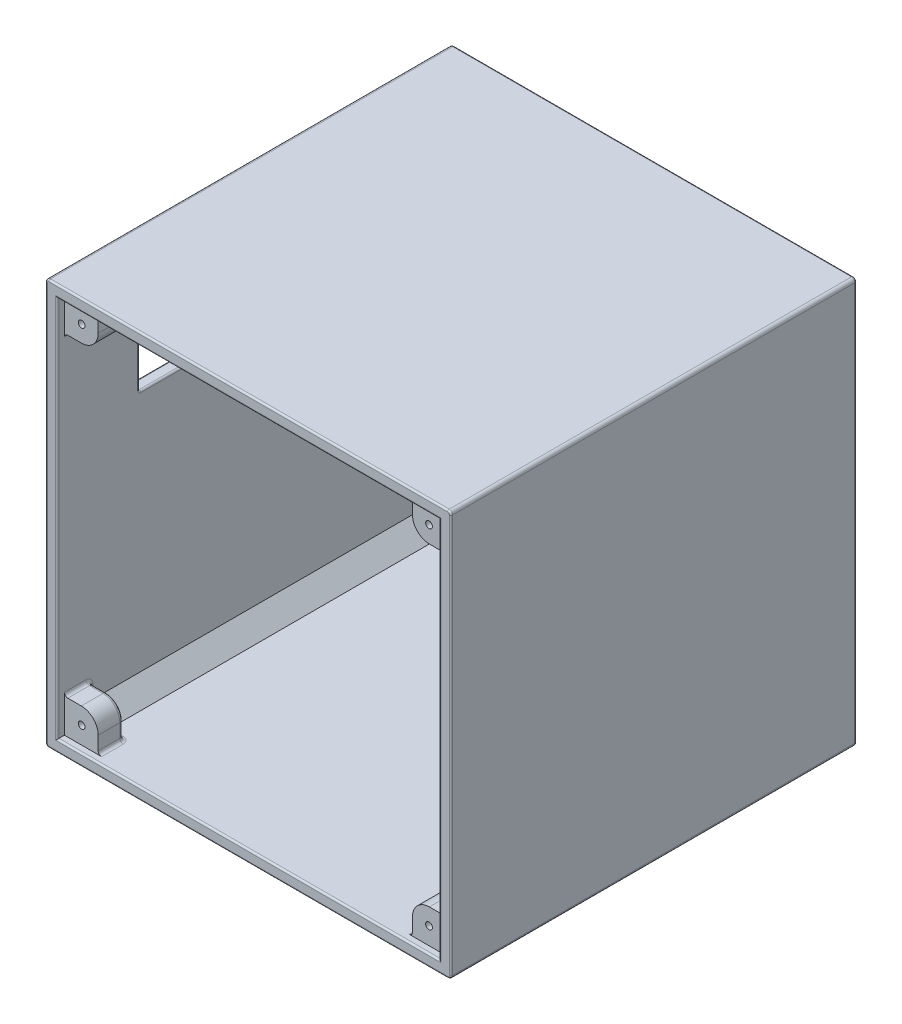
SolidWorks part; units mm, degrees
material "PVC 0.007 Plasticizado"
ref_plane "Plano frontal" through (0, 0, 0) normal (0, 0, 1) x (1, 0, 0)
ref_plane "Plano superior" through (0, 0, 0) normal (0, 1, 0) x (1, 0, 0)
ref_plane "Plano direito" through (0, 0, 0) normal (1, 0, 0) x (0, 0, -1)
sketch "Esboço2" plane through (0, 0, 0) normal (0, 0, 1) x (1, 0, 0)
  line L1 (-60, -60) -> (60, -60)
  line L2 (-60, -60) -> (-60, 60)
  line L3 (-60, 60) -> (60, 60)
  line L4 (60, -60) -> (60, 60)
  line L5 (-60, -60) -> (60, 60) construction
  line L6 (-60, 60) -> (60, -60) construction
  point P0 (0, 0)
extrude "Ressalto-extrusão1" add sketch "Esboço2" along normal blind 120
sketch "Esboço3" plane through (0, 0, 120) normal (0, 0, 1) x (1, 0, 0)
  line L8 (56.5, -56.5) -> (56.5, 56.5)
  line L9 (56.5, 56.5) -> (-56.5, 56.5)
  line L10 (-56.5, 56.5) -> (-56.5, -56.5)
  line L11 (-56.5, -56.5) -> (56.5, -56.5)
  line L12 (56.5, -56.5) -> (56.5, 56.5)
  line L13 (56.5, 56.5) -> (-56.5, 56.5)
  line L14 (-56.5, 56.5) -> (-56.5, -56.5)
  line L15 (-56.5, -56.5) -> (56.5, -56.5)
  dimension "D1" = 3.5
extrude "Corte-extrusão1" cut sketch "Esboço3" against normal blind 120
ref_plane "Plano1" through (0, 0, 0) normal (0, 0, 1) x (1, 0, 0)
ref_plane "Plano2" through (0, 0, 116.5) normal (0, 0, 1) x (1, 0, 0)
sketch "Esboço4" plane through (0, 0, 0) normal (0, 0, 1) x (1, 0, 0)
  line L0 (56.5, 56.5) -> (-56.5, 56.5) construction
  line L1 (-56.5, 56.5) -> (-56.5, -56.5) construction
  line L2 (-51.5, 46.5) -> (-56.5, 46.5)
  line L3 (-56.5, 46.5) -> (-56.5, 56.5)
  line L4 (-56.5, 56.5) -> (-46.5, 56.5)
  line L5 (-46.5, 56.5) -> (-46.5, 51.5)
  line L6 (0, -66) -> (0, 66) construction
  line L7 (46.5, 56.5) -> (46.5, 51.5)
  line L8 (56.5, 56.5) -> (46.5, 56.5)
  line L9 (56.5, 46.5) -> (56.5, 56.5)
  line L10 (51.5, 46.5) -> (56.5, 46.5)
  line L11 (66, 0) -> (-66, 0) construction
  line L12 (51.5, -46.5) -> (56.5, -46.5)
  line L13 (56.5, -46.5) -> (56.5, -56.5)
  line L14 (56.5, -56.5) -> (46.5, -56.5)
  line L15 (46.5, -56.5) -> (46.5, -51.5)
  line L16 (-46.5, -56.5) -> (-46.5, -51.5)
  line L17 (-56.5, -56.5) -> (-46.5, -56.5)
  line L18 (-56.5, -46.5) -> (-56.5, -56.5)
  line L19 (-51.5, -46.5) -> (-56.5, -46.5)
  line L20 (-51.5, 5) -> (-56.5, 5)
  line L21 (-56.5, 5) -> (-56.5, -5)
  line L22 (-56.5, -5) -> (-51.5, -5)
  line L23 (56.5, -5) -> (51.5, -5)
  line L24 (56.5, 5) -> (56.5, -5)
  line L25 (51.5, 5) -> (56.5, 5)
  line L26 (-5, 51.5) -> (-5, 56.5)
  line L27 (-5, 56.5) -> (5, 56.5)
  line L28 (5, 56.5) -> (5, 51.5)
  arc A0 (-51.5, 46.5) -> (-46.5, 51.5) centre (-51.5, 51.5) ccw
  arc A1 (51.5, 46.5) -> (46.5, 51.5) centre (51.5, 51.5) cw
  arc A2 (51.5, -46.5) -> (46.5, -51.5) centre (51.5, -51.5) ccw
  arc A3 (-51.5, -46.5) -> (-46.5, -51.5) centre (-51.5, -51.5) cw
  arc A4 (-51.5, -5) -> (-51.5, 5) centre (-51.5, 0) ccw
  arc A5 (51.5, -5) -> (51.5, 5) centre (51.5, 0) cw
  arc A6 (-5, 51.5) -> (5, 51.5) centre (0, 51.5) ccw
  dimension "D1" = 10
  dimension "D2" = 10
  dimension "D3" = 10
extrude "Ressalto-extrusão2" add sketch "Esboço4" along normal blind 7
sketch "Esboço5" plane through (0, 0, 116.5) normal (0, 0, 1) x (1, 0, 0)
  line L0 (-51.5, 46.5) -> (-56.5, 46.5)
  line L1 (-56.5, 46.5) -> (-56.5, 56.5)
  line L2 (-56.5, 56.5) -> (-46.5, 56.5)
  line L3 (-46.5, 56.5) -> (-46.5, 51.5)
  line L4 (46.5, 56.5) -> (46.5, 51.5)
  line L5 (56.5, 56.5) -> (46.5, 56.5)
  line L6 (56.5, 46.5) -> (56.5, 56.5)
  line L7 (51.5, 46.5) -> (56.5, 46.5)
  line L8 (51.5, -46.5) -> (56.5, -46.5)
  line L9 (56.5, -46.5) -> (56.5, -56.5)
  line L10 (56.5, -56.5) -> (46.5, -56.5)
  line L11 (46.5, -56.5) -> (46.5, -51.5)
  line L12 (-46.5, -56.5) -> (-46.5, -51.5)
  line L13 (-56.5, -56.5) -> (-46.5, -56.5)
  line L14 (-56.5, -46.5) -> (-56.5, -56.5)
  line L15 (-51.5, -46.5) -> (-56.5, -46.5)
  arc A0 (-51.5, 46.5) -> (-46.5, 51.5) centre (-51.5, 51.5) ccw
  arc A1 (51.5, 46.5) -> (46.5, 51.5) centre (51.5, 51.5) cw
  arc A2 (51.5, -46.5) -> (46.5, -51.5) centre (51.5, -51.5) ccw
  arc A3 (-51.5, -46.5) -> (-46.5, -51.5) centre (-51.5, -51.5) cw
  dimension "D1" = 10
ref_plane "Plano5" through (0, 0, 117.9) normal (0, 0, 1) x (1, 0, 0)
sketch "Esboço13" plane through (0, 0, 0) normal (0, 0, 1) x (1, 0, 0)
  line L0 (-56.5, -56.5) -> (56.5, -56.5) construction
  line L1 (-5, -51.5) -> (-5, -56.5)
  line L2 (-5, -56.5) -> (5, -56.5)
  line L3 (5, -56.5) -> (5, -51.5)
  arc A0 (5, -51.5) -> (-5, -51.5) centre (0, -51.5) ccw
  dimension "D1" = 10
extrude "Ressalto-extrusão6" add sketch "Esboço13" along normal blind 7
chamfer "Chanfro1" distance 5 angle 45 1 edges at (-56.5, 56.5, 63.5)
chamfer "Chanfro2" distance 5 angle 45 3 edges at (-56.5, -56.5, 63.5) (56.5, -56.5, 63.5) (56.5, 56.5, 63.5)
sketch "Esboço14" plane through (-60, 0, 0) normal (-1, 0, 0) x (0, 0, 1)
  line L0 (120, 60) -> (0, 60) construction
  line L1 (24.25, 45) -> (95.75, 45)
  line L2 (24.25, 45) -> (24.25, 20.5)
  line L3 (24.25, 20.5) -> (95.75, 20.5)
  line L4 (95.75, 45) -> (95.75, 20.5)
  line L5 (24.25, 45) -> (95.75, 20.5) construction
  line L6 (24.25, 20.5) -> (95.75, 45) construction
  point P0 (60, 32.75)
  point P8 (60, 60)
  dimension "D1" = 71.5
  dimension "D2" = 24.5
  dimension "D3" = 15
extrude "Corte-extrusão6" cut sketch "Esboço14" against normal blind 10
sketch "Esboço15" plane through (0, 0, 120) normal (0, 0, 1) x (1, 0, 0)
  line L1 (-56.5, -56.5) -> (56.5, -56.5)
  line L2 (-56.5, -56.5) -> (-56.5, 56.5)
  line L3 (-56.5, 56.5) -> (56.5, 56.5)
  line L4 (56.5, -56.5) -> (56.5, 56.5)
  line L5 (-56.5, -56.5) -> (56.5, 56.5) construction
  line L6 (-56.5, 56.5) -> (56.5, -56.5) construction
  point P0 (0, 0)
  dimension "D1" = 113
extrude "Corte-extrusão7" cut sketch "Esboço15" against normal blind 5
fillet "Filete3" radius 1 1 edges at (-60, 60, 60)
fillet "Filete4" radius 1 3 edges at (60, 60, 60) (60, -60, 60) (-60, -60, 60)
extrude "Ressalto-extrusão7" add sketch "Esboço5" against normal blind 6 and the other way blind 1.4
fillet "Filete8" radius 1 88 edges at (56.5, 46.5, 3.5) (46.5, 56.5, 3.5) (54, 46.5, 7) (47.9645, 47.9645, 7) (46.5, 54, 7) (49, 56.5, 7) (54, 54, 7) (56.5, 49, 7) (56.5, -46.5, 114.2) (46.5, -56.5, 114.2) (-46.5, -56.5, 114.2) (-56.5, -46.5, 114.2) (-56.5, 46.5, 114.2) (-46.5, 56.5, 114.2) (46.5, 56.5, 114.2) (56.5, 46.5, 114.2) (56.5, 5, 3.5) (56.5, -5, 3.5) (46.5, -56.5, 3.5) (56.5, -46.5, 3.5) (5, -56.5, 3.5) (-5, -56.5, 3.5) (-56.5, -46.5, 3.5) (-46.5, -56.5, 3.5) (-56.5, -5, 3.5) (-56.5, 5, 3.5) (-46.5, 56.5, 3.5) (-56.5, 46.5, 3.5) (-5, 56.5, 3.5) (5, 56.5, 3.5) (54, -46.5, 110.5) (47.9645, -47.9645, 110.5) (46.5, -54, 110.5) (49, -56.5, 110.5) (54, -54, 110.5) (56.5, -49, 110.5) (-49, -56.5, 110.5) (-46.5, -54, 110.5) (-47.9645, -47.9645, 110.5) (-54, -46.5, 110.5) (-56.5, -49, 110.5) (-54, -54, 110.5) (-54, 46.5, 110.5) (-47.9645, 47.9645, 110.5) (-46.5, 54, 110.5) (-49, 56.5, 110.5) (-54, 54, 110.5) (-56.5, 49, 110.5) (49, 56.5, 110.5) (46.5, 54, 110.5) (47.9645, 47.9645, 110.5) (54, 46.5, 110.5) (56.5, 49, 110.5) (54, 54, 110.5) (54, 5, 7) (56.5, 0, 7) (54, -5, 7) (46.5, 0, 7) (46.5, -54, 7) (47.9645, -47.9645, 7) (54, -46.5, 7) (56.5, -49, 7) (54, -54, 7) (49, -56.5, 7) (5, -54, 7) (0, -56.5, 7) (-5, -54, 7) (0, -46.5, 7) (-54, -46.5, 7) (-47.9645, -47.9645, 7) (-46.5, -54, 7) (-49, -56.5, 7) (-54, -54, 7) (-56.5, -49, 7) (-54, -5, 7) (-56.5, 0, 7) (-54, 5, 7) (-46.5, 0, 7) (-46.5, 54, 7) (-47.9645, 47.9645, 7) (-54, 46.5, 7) (-56.5, 49, 7) (-54, 54, 7) (-49, 56.5, 7) (0, 46.5, 7) (-5, 54, 7) (0, 56.5, 7) (5, 54, 7)
sketch "Esboço16" plane through (0, 0, 117.9) normal (0, 0, 1) x (1, 0, 0)
  line L0 (59, 60) -> (-59, 60) construction
  line L1 (-60, 59) -> (-60, -59) construction
  circle A0 centre (-51.4, 51.4) radius 1
  dimension "D1" = 2
  dimension "D2" = 8.6
  dimension "D3" = 8.6
extrude "Corte-extrusão8" cut sketch "Esboço16" against normal up to next
mirror "Espelhar1" about plane through (0, 0, 0) normal (0, 1, 0) of "Corte-extrusão8"
mirror "Espelhar2" about plane through (0, 0, 0) normal (1, 0, 0) of "Espelhar1"
sketch "Esboço17" plane through (0, 0, 7) normal (0, 0, 1) x (1, 0, 0)
  line L0 (59, 60) -> (-59, 60) construction
  line L1 (-60, 59) -> (-60, -59) construction
  circle A0 centre (-51.4, 51.4) radius 1.75
  point P4 (0, 0)
  point P6 (-59.5508, 49.8209)
  dimension "D1" = 8.6
  dimension "D2" = 8.6
extrude "Corte-extrusão9" cut sketch "Esboço17" against normal up to next
sketch "Esboço18" plane through (0, 0, 7) normal (0, 0, 1) x (1, 0, 0)
  circle A0 centre (-51.4, 51.4) radius 3.6
  circle A1 centre (-51.4, 51.4) radius 1.75 construction
  dimension "D1" = 7.2
extrude "Corte-extrusão10" cut sketch "Esboço18" against normal blind 1 and the other way blind 1
mirror "Espelhar5" about plane through (0, 0, 0) normal (0, 1, 0) of "Corte-extrusão10", "Corte-extrusão9"
mirror "Espelhar6" about plane through (0, 0, 0) normal (1, 0, 0) of "Espelhar5"
sketch "Esboço19" plane through (0, 0, 7) normal (0, 0, 1) x (1, 0, 0)
  line L0 (-60, 59) -> (-60, -59) construction
  line L2 (59, 60) -> (-59, 60) construction
  line L3 (60, -59) -> (60, 59) construction
  line L5 (-59, -60) -> (59, -60) construction
  circle A0 centre (-51.4, 0) radius 3.6
  circle A4 centre (0, 51.4) radius 3.6
  circle A5 centre (51.4, 0) radius 3.6
  circle A6 centre (0, -51.4) radius 3.6
  point P6 (0, 51.5)
  point P10 (0, 0)
  point P11 (51.5, 0)
  point P13 (0, 0)
  point P16 (0, 0)
  point P17 (0, 0)
  point P18 (0, -51.467)
  point P19 (0, 0)
  point P20 (-0.3388, 52.5729)
  point P21 (0, 0)
  point P25 (53.3243, 0)
  point P28 (0, -52.7165)
  dimension "D1" = 8.6
  dimension "D3" = 8.6
  dimension "D4" = 7.2
  dimension "D5" = 7.2
  dimension "D6" = 7.2
  dimension "D7" = 7.2
  dimension "8.6" = 8.6
  dimension "D2" = 8.6
extrude "Corte-extrusão12" cut sketch "Esboço19" against normal blind 0.5
sketch "Esboço21" plane through (0, 0, 6.5) normal (0, 0, 1) x (1, 0, 0)
  line L1 (59, 60) -> (-59, 60) construction
  line L2 (60, -59) -> (60, 59) construction
  line L3 (-59, -60) -> (59, -60) construction
  circle A0 centre (-51.4, 0) radius 1.75
  circle A1 centre (0, 51.4) radius 1.75
  circle A2 centre (51.4, 0) radius 1.75
  circle A3 centre (0, -51.4) radius 1.75
  point P5 (0, 52.5493)
  point P10 (53.2353, 0)
  point P15 (0, -52.878)
  dimension "D1" = 3.5
  dimension "D2" = 8.6
  dimension "D3" = 8.6
  dimension "D4" = 8.6
extrude "Corte-extrusão13" cut sketch "Esboço21" against normal through all
fillet "Filete9" radius 0.5 88 edges at (-59.7071, 59.7071, 0) (-60, 0, 0) (-59.7071, -59.7071, 0) (0, -60, 0) (59.7071, -59.7071, 0) (60, 0, 0) (59.7071, 59.7071, 0) (0, 60, 0) (47.9645, -47.9645, 0) (46.5, -53.5, 0) (46.2071, -56.2071, 0) (25.75, -56.5, 0) (5.2929, -56.2071, 0) (5, -53.5, 0) (0, -46.5, 0) (-5, -53.5, 0) (-5.2929, -56.2071, 0) (-25.75, -56.5, 0) (-46.2071, -56.2071, 0) (-46.5, -53.5, 0) (-47.9645, -47.9645, 0) (-53.5, -46.5, 0) (-56.2071, -46.2071, 0) (-56.5, -25.75, 0) (-56.2071, -5.2929, 0) (-53.5, -5, 0) (-46.5, 0, 0) (-53.5, 5, 0) (-56.2071, 5.2929, 0) (-56.5, 25.75, 0) (-56.2071, 46.2071, 0) (-53.5, 46.5, 0) (-47.9645, 47.9645, 0) (-46.5, 53.5, 0) (-46.2071, 56.2071, 0) (-25.75, 56.5, 0) (-5.2929, 56.2071, 0) (-5, 53.5, 0) (0, 46.5, 0) (5, 53.5, 0) (5.2929, 56.2071, 0) (25.75, 56.5, 0) (46.2071, 56.2071, 0) (46.5, 53.5, 0) (47.9645, 47.9645, 0) (53.5, 46.5, 0) (56.2071, 46.2071, 0) (56.5, 25.75, 0) (56.2071, 5.2929, 0) (53.5, 5, 0) (46.5, 0, 0) (53.5, -5, 0) (56.2071, -5.2929, 0) (56.5, -25.75, 0) (56.2071, -46.2071, 0) (53.5, -46.5, 0) (-53.15, 51.4, 0) (-53.15, -51.4, 0) (49.65, -51.4, 0) (49.65, 51.4, 0) (1.75, -51.4, 0) (53.15, 0, 0) (1.75, 51.4, 0) (-49.65, 0, 0) (-56.5, 20.5, 60) (-60, 20.5, 60) (-56.5, 32.75, 95.75) (-60, 32.75, 95.75) (-58.25, 20.5, 95.75) (-56.5, 45, 60) (-60, 45, 60) (-58.25, 45, 95.75) (-56.5, 32.75, 24.25) (-58.25, 20.5, 24.25) (-60, 32.75, 24.25) (-58.25, 45, 24.25) (59.7071, -59.7071, 120) (0, -60, 120) (-59.7071, -59.7071, 120) (-60, 0, 120) (-59.7071, 59.7071, 120) (0, 60, 120) (59.7071, 59.7071, 120) (60, 0, 120) (0, 56.5, 120) (-56.5, 0, 120) (0, -56.5, 120) (56.5, 0, 120)
